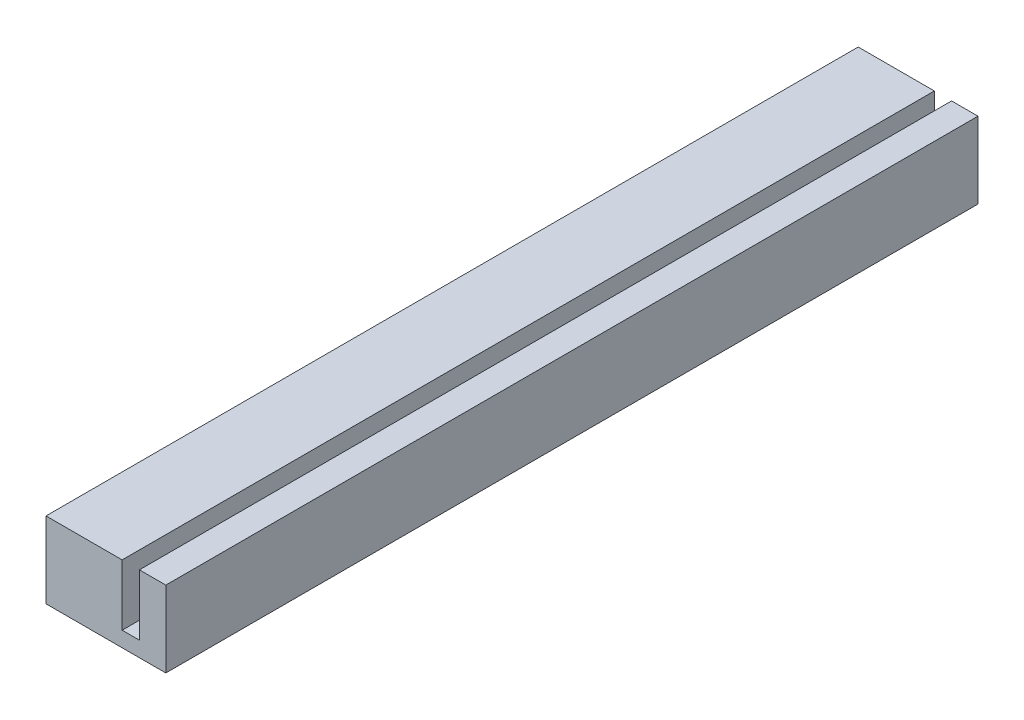
SolidWorks part; units mm, degrees
ref_plane "Front Plane" through (0, 0, 0) normal (0, 0, 1) x (1, 0, 0)
ref_plane "Top Plane" through (0, 0, 0) normal (0, 1, 0) x (1, 0, 0)
ref_plane "Right Plane" through (0, 0, 0) normal (1, 0, 0) x (0, 0, -1)
sketch "Sketch1" plane through (0, 0, 0) normal (0, 1, 0) x (1, 0, 0)
  line L1 (-3.762, 1.9862) -> (8.038, 1.9862)
  line L2 (-3.762, 1.9862) -> (-3.762, -78.0138)
  line L3 (-3.762, -78.0138) -> (8.038, -78.0138)
  line L4 (8.038, 1.9862) -> (8.038, -78.0138)
  dimension "D1" = 11.8
  dimension "D2" = 80
extrude "Boss-Extrude1" add sketch "Sketch1" along normal blind 1.5
sketch "Sketch2" plane through (0, 1.5, 0) normal (0, 1, 0) x (1, 0, 0)
  line L0 (8.038, 1.9862) -> (-3.762, 1.9862) construction
  line L1 (-3.762, 1.9862) -> (3.738, 1.9862)
  line L2 (-3.762, 1.9862) -> (-3.762, -78.0138)
  line L3 (-3.762, -78.0138) -> (3.738, -78.0138)
  line L4 (3.738, 1.9862) -> (3.738, -78.0138)
  line L5 (-3.762, -78.0138) -> (8.038, -78.0138) construction
  line L6 (-3.762, 1.9862) -> (-3.762, -78.0138) construction
  line L8 (5.438, 1.9862) -> (8.038, 1.9862)
  line L9 (5.438, 1.9862) -> (5.438, -78.0138)
  line L10 (5.438, -78.0138) -> (8.038, -78.0138)
  line L11 (8.038, 1.9862) -> (8.038, -78.0138)
  dimension "D1" = 0
  dimension "D2" = 7.5
  dimension "D3" = 1.7
extrude "Boss-Extrude2" add sketch "Sketch2" along normal blind 6
